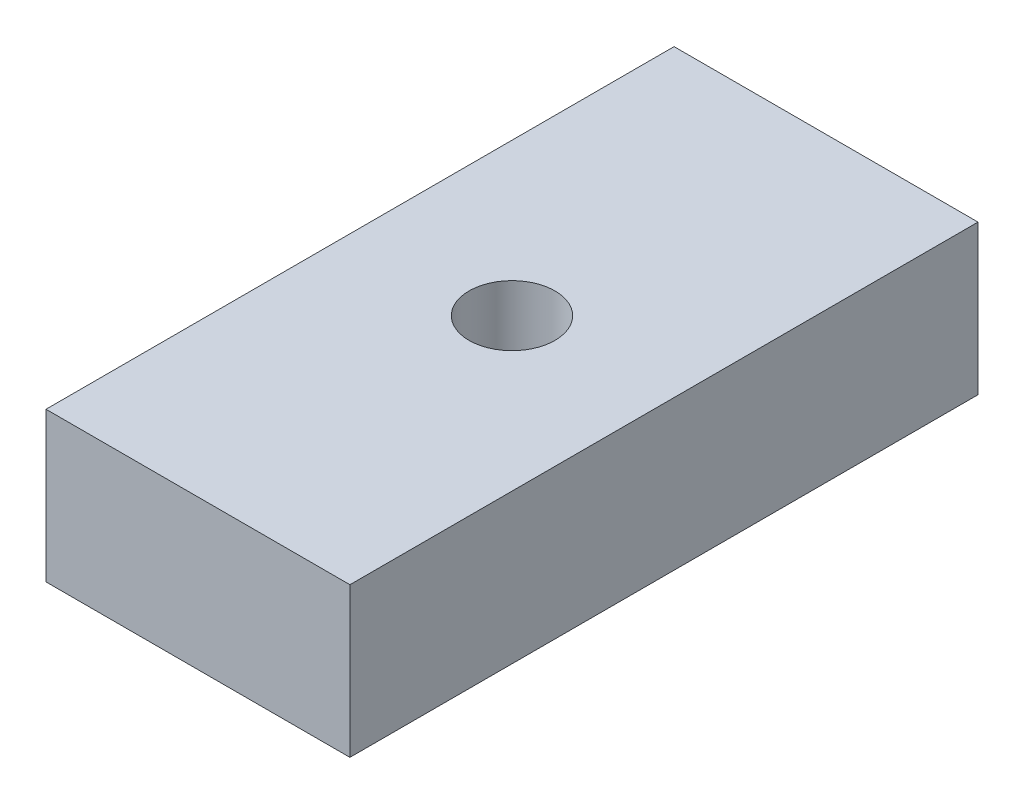
SolidWorks part; units mm, degrees
ref_plane "XY" through (0, 0, 0) normal (0, 0, 1) x (1, 0, 0)
ref_plane "XZ" through (0, 0, 0) normal (0, 1, 0) x (1, 0, 0)
ref_plane "YZ" through (0, 0, 0) normal (1, 0, 0) x (0, 0, -1)
ref_axis "X" through (-88.99, 0, 0) along (1, 0, 0)
ref_axis "Y" through (0, -55, 0) along (0, 1, 0)
ref_axis "Z" through (0, 0, 55) along (0, 0, -1)
sketch "Sketch1" plane through (0, 0, 0) normal (0, 1, 0) x (1, 0, 0)
  line L1 (-4.0005, -8.2677) -> (4.0005, -8.2677)
  line L2 (-4.0005, -8.2677) -> (-4.0005, 8.2677)
  line L3 (-4.0005, 8.2677) -> (4.0005, 8.2677)
  line L4 (4.0005, -8.2677) -> (4.0005, 8.2677)
  line L5 (-4.0005, -8.2677) -> (4.0005, 8.2677) construction
  line L6 (-4.0005, 8.2677) -> (4.0005, -8.2677) construction
  point P0 (0, 0)
  dimension "D1" = 16.5354
  dimension "D2" = 8.001
extrude "Boss-Extrude1" add sketch "Sketch1" along normal blind 3.937
hole_wizard "#4-40 Tapped Hole1" positions "Sketch2" profile "Sketch3" tap size "#4-40" standard "ANSI Inch" end condition through all
sketch "Sketch2" plane through (0, 3.937, 0) normal (0, 1, 0) x (1, 0, 0)
  point P0 (0, 0)
sketch "Sketch3" plane through (0, 3.937, 0) normal (1, 0, 0) x (0, 0, 1)
  line L0 (0, 0) -> (0, 3.937)
  line L1 (0, 3.937) -> (1.1303, 3.937)
  line L2 (1.1303, 3.937) -> (1.1303, 0)
  line L5 (1.1303, 0) -> (0, 0)
  line L11 (0, -6.35) -> (0, 107.95) construction
  dimension "Thru Tap Drill Dia." = 2.2606
  dimension "Thru Tap Drill Depth" = 3.937
cosmetic thread "Hole Thread1"
